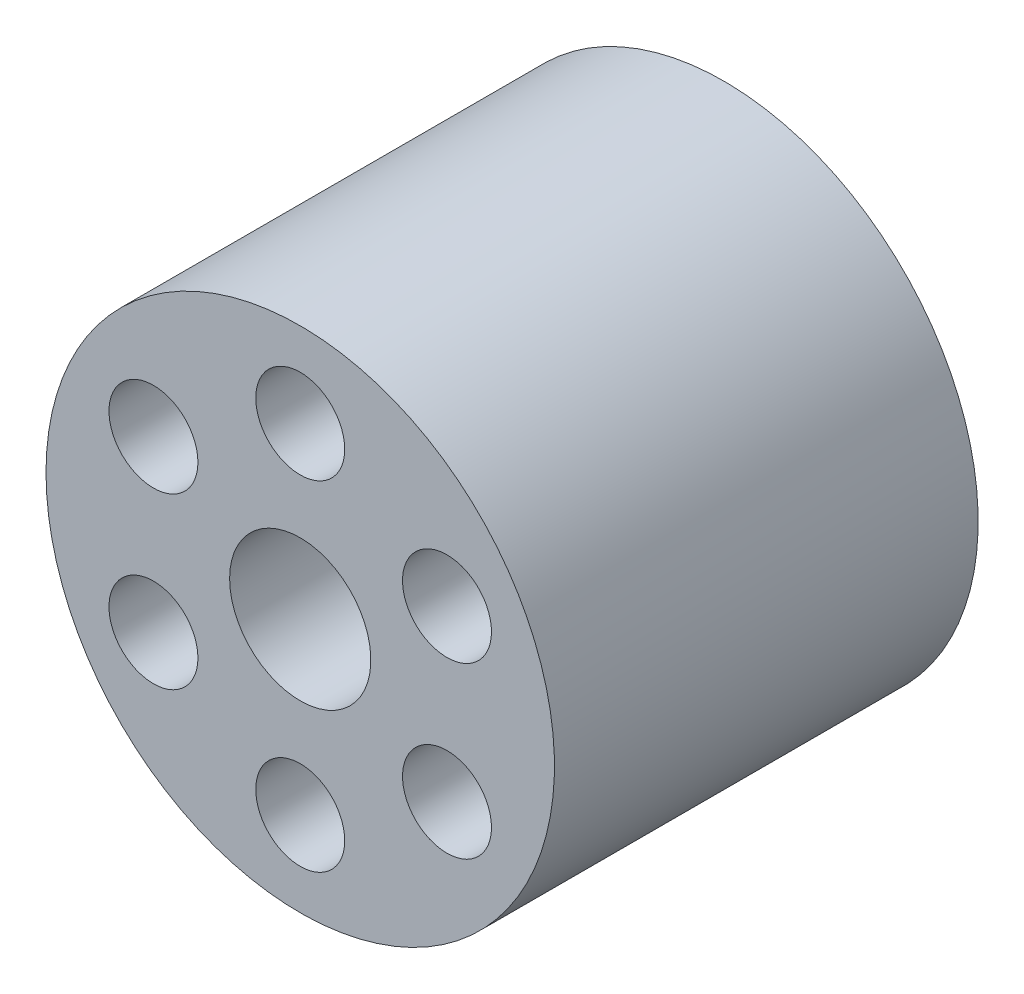
SolidWorks part; units mm, degrees
ref_plane "Front Plane" through (0, 0, 0) normal (0, 0, 1) x (1, 0, 0)
ref_plane "Top Plane" through (0, 0, 0) normal (0, 1, 0) x (1, 0, 0)
ref_plane "Right Plane" through (0, 0, 0) normal (1, 0, 0) x (0, 0, -1)
sketch "Sketch1" plane through (0, 0, 0) normal (0, 0, 1) x (1, 0, 0)
  circle A0 centre (0, 0) radius 11.43
  circle A1 centre (0, 0) radius 3.175
extrude "Boss-Extrude1" add sketch "Sketch1" along normal blind 19.05
sketch "Sketch4" plane through (0, 0, 19.05) normal (0, 0, 1) x (1, 0, 0)
  line L0 (0, -55) -> (0, 55) construction
  point P0 (0, 7.62)
hole_wizard "Ø4.0mm Dowel Hole2" positions "Sketch4" profile "Sketch5" hole size "Ø4.0" standard "ANSI Metric" end condition through all
sketch "Sketch5" plane through (0, 7.62, 19.05) normal (1, 0, 0) x (0, -1, 0)
  line L0 (0, 0) -> (0, 19.05)
  line L1 (0, 19.05) -> (2, 19.05)
  line L2 (2, 19.05) -> (2, 0)
  line L5 (2, 0) -> (0, 0)
  line L11 (0, -6.35) -> (0, 107.95) construction
  dimension "Thru Hole Dia." = 4
  dimension "Thru Hole Depth" = 19.05
pattern_circular "CirPattern1" count 6 over 360 about axis through (0, 0, 19.05) along (0, 0, -1) of "Ø4.0mm Dowel Hole2" reverse direction yes
